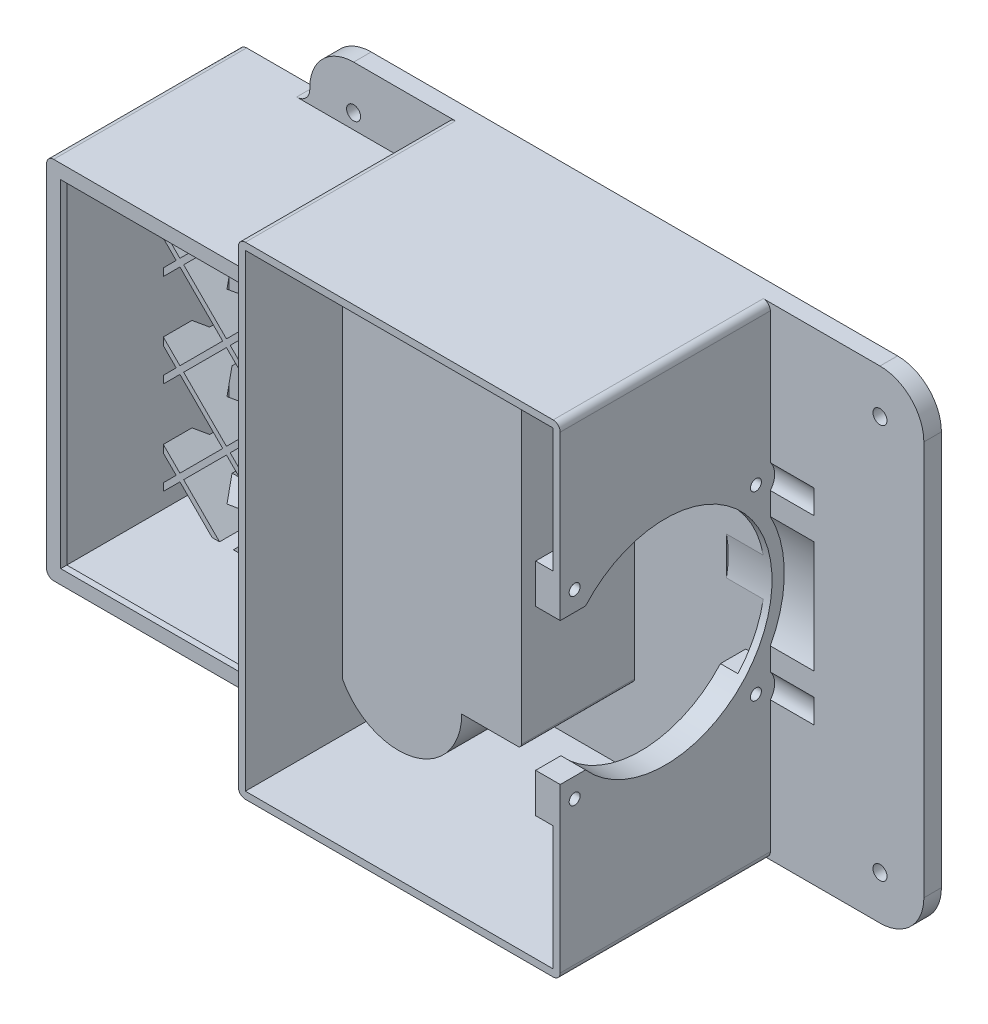
SolidWorks part; units mm, degrees
ref_plane "Front Plane" through (0, 0, 0) normal (0, 0, 1) x (1, 0, 0)
ref_plane "Top Plane" through (0, 0, 0) normal (0, 1, 0) x (1, 0, 0)
ref_plane "Right Plane" through (0, 0, 0) normal (1, 0, 0) x (0, 0, -1)
sketch "Sketch11" plane through (0, 0, 0) normal (0, 0, 1) x (1, 0, 0)
  line L0 (-18.2, 15.22) -> (0, 15.22)
  line L1 (0, 15.22) -> (0, 13.61)
  line L2 (-18.2, 13.61) -> (0, 13.61)
  line L3 (-18.2, 0) -> (0, 0)
  line L4 (0, 0) -> (0, 1.61)
  line L5 (-18.2, 1.61) -> (0, 1.61)
  line L6 (-25.81, 7.61) -> (0, 7.61)
  arc A0 (-18.2, 13.61) -> (-18.2, 1.61) centre (-18.2, 7.61) ccw
  arc A1 (-18.2, 15.22) -> (-18.2, 0) centre (-18.2, 7.61) ccw
sketch "Sketch1" plane through (0, 0, 0) normal (0, 0, 1) x (1, 0, 0)
  line L1 (160, 10) -> (160, 100)
  line L2 (150, 0) -> (30, 0)
  line L3 (20, 10) -> (20, 10.39)
  line L4 (150, 110) -> (30, 110)
  line L10 (1.61, 96.61) -> (17, 96.61)
  line L11 (17, 13.39) -> (1.61, 13.39)
  line L12 (0, 15) -> (0, 95)
  line L17 (20, 99.61) -> (20, 100)
  circle A8 centre (30, 10) radius 1.6
  circle A9 centre (30, 100) radius 1.6
  circle A10 centre (150, 10) radius 1.6
  circle A11 centre (150, 100) radius 1.6
  arc A12 (1.61, 96.61) -> (0, 95) centre (1.61, 95) ccw
  arc A14 (0, 15) -> (1.61, 13.39) centre (1.61, 15) ccw
  arc A16 (17, 96.61) -> (20, 99.61) centre (17, 99.61) ccw
  arc A17 (17, 13.39) -> (20, 10.39) centre (17, 10.39) cw
  arc A18 (20, 10) -> (30, 0) centre (30, 10) ccw
  arc A19 (30, 110) -> (20, 100) centre (30, 100) ccw
  arc A20 (160, 100) -> (150, 110) centre (150, 100) ccw
  arc A21 (150, 0) -> (160, 10) centre (150, 10) ccw
extrude "Boss-Extrude1" add sketch "Sketch1" along normal blind 4
sketch "Sketch3" plane through (0, 0, 4) normal (0, 0, 1) x (1, 0, 0)
  line L0 (1.61, 83.8886) -> (1.61, 82.1774)
  line L2 (19.2854, 95) -> (26.61, 87.6754)
  line L3 (26.61, 87.6754) -> (33.9346, 95)
  line L5 (33.9346, 95) -> (35.6458, 95)
  line L6 (17.5742, 95) -> (19.2854, 95)
  line L7 (6.2524, 86.8198) -> (14.4326, 95)
  line L8 (6.2524, 86.8198) -> (16.0034, 77.0688)
  line L9 (16.0034, 77.0688) -> (25.7544, 86.8198)
  line L10 (17.5742, 95) -> (25.7544, 86.8198)
  line L11 (38.7874, 95) -> (40.4986, 95)
  line L12 (51.61, 83.8886) -> (51.61, 82.1774)
  line L13 (1.61, 82.1774) -> (5.3968, 85.9642)
  line L14 (1.61, 70.249) -> (5.3968, 66.4622)
  line L15 (5.3968, 66.4622) -> (15.1478, 76.2132)
  line L16 (5.3968, 85.9642) -> (15.1478, 76.2132)
  line L17 (51.61, 70.249) -> (51.61, 68.5378)
  line L18 (1.61, 70.249) -> (1.61, 68.5378)
  line L21 (1.61, 62.6754) -> (4.5412, 65.6066)
  line L22 (1.61, 68.5378) -> (4.5412, 65.6066)
  line L23 (1.61, 62.6754) -> (1.61, 60.9642)
  line L24 (1.61, 49.0358) -> (1.61, 47.3246)
  line L29 (1.61, 41.4622) -> (1.61, 39.751)
  line L30 (1.61, 27.8226) -> (1.61, 26.1114)
  line L35 (1.61, 20.249) -> (1.61, 18.5378)
  line L36 (33.9346, 15) -> (35.6458, 15)
  line L37 (27.4656, 86.8198) -> (35.6458, 95)
  line L38 (27.4656, 86.8198) -> (37.2166, 77.0688)
  line L39 (37.2166, 77.0688) -> (46.9676, 86.8198)
  line L40 (38.7874, 95) -> (46.9676, 86.8198)
  line L41 (17.5742, 15) -> (19.2854, 15)
  line L42 (38.7874, 15) -> (40.4986, 15)
  line L43 (16.859, 76.2132) -> (26.61, 85.9642)
  line L44 (16.859, 76.2132) -> (26.61, 66.4622)
  line L45 (26.61, 66.4622) -> (36.361, 76.2132)
  line L46 (26.61, 85.9642) -> (36.361, 76.2132)
  line L47 (51.61, 20.249) -> (51.61, 18.5378)
  line L48 (51.61, 27.8226) -> (51.61, 26.1114)
  line L49 (6.2524, 65.6066) -> (16.0034, 75.3576)
  line L50 (6.2524, 65.6066) -> (16.0034, 55.8556)
  line L51 (16.0034, 55.8556) -> (25.7544, 65.6066)
  line L52 (16.0034, 75.3576) -> (25.7544, 65.6066)
  line L53 (51.61, 41.4622) -> (51.61, 39.751)
  line L54 (51.61, 49.0358) -> (51.61, 47.3246)
  line L55 (1.61, 60.9642) -> (5.3968, 64.751)
  line L56 (1.61, 49.0358) -> (5.3968, 45.249)
  line L57 (5.3968, 45.249) -> (15.1478, 55)
  line L58 (5.3968, 64.751) -> (15.1478, 55)
  line L59 (51.61, 62.6754) -> (51.61, 60.9642)
  line L63 (1.61, 41.4622) -> (4.5412, 44.3934)
  line L64 (1.61, 47.3246) -> (4.5412, 44.3934)
  line L73 (38.0722, 76.2132) -> (47.8232, 85.9642)
  line L74 (38.0722, 76.2132) -> (47.8232, 66.4622)
  line L75 (47.8232, 66.4622) -> (51.61, 70.249)
  line L76 (47.8232, 85.9642) -> (51.61, 82.1774)
  line L79 (27.4656, 65.6066) -> (37.2166, 75.3576)
  line L80 (27.4656, 65.6066) -> (37.2166, 55.8556)
  line L81 (37.2166, 55.8556) -> (46.9676, 65.6066)
  line L82 (37.2166, 75.3576) -> (46.9676, 65.6066)
  line L85 (16.859, 55) -> (26.61, 64.751)
  line L86 (16.859, 55) -> (26.61, 45.249)
  line L87 (26.61, 45.249) -> (36.361, 55)
  line L88 (26.61, 64.751) -> (36.361, 55)
  line L91 (6.2524, 44.3934) -> (16.0034, 54.1444)
  line L92 (6.2524, 44.3934) -> (16.0034, 34.6424)
  line L93 (16.0034, 34.6424) -> (25.7544, 44.3934)
  line L94 (16.0034, 54.1444) -> (25.7544, 44.3934)
  line L97 (1.61, 39.751) -> (5.3968, 43.5378)
  line L98 (1.61, 27.8226) -> (5.3968, 24.0358)
  line L99 (5.3968, 24.0358) -> (15.1478, 33.7868)
  line L100 (5.3968, 43.5378) -> (15.1478, 33.7868)
  line L105 (1.61, 20.249) -> (4.5412, 23.1802)
  line L106 (1.61, 26.1114) -> (4.5412, 23.1802)
  line L109 (48.6788, 65.6066) -> (51.61, 68.5378)
  line L110 (48.6788, 65.6066) -> (51.61, 62.6754)
  line L115 (38.0722, 55) -> (47.8232, 64.751)
  line L116 (38.0722, 55) -> (47.8232, 45.249)
  line L117 (47.8232, 45.249) -> (51.61, 49.0358)
  line L118 (47.8232, 64.751) -> (51.61, 60.9642)
  line L121 (27.4656, 44.3934) -> (37.2166, 54.1444)
  line L122 (27.4656, 44.3934) -> (37.2166, 34.6424)
  line L123 (37.2166, 34.6424) -> (46.9676, 44.3934)
  line L124 (37.2166, 54.1444) -> (46.9676, 44.3934)
  line L127 (16.859, 33.7868) -> (26.61, 43.5378)
  line L128 (16.859, 33.7868) -> (26.61, 24.0358)
  line L129 (26.61, 24.0358) -> (36.361, 33.7868)
  line L130 (26.61, 43.5378) -> (36.361, 33.7868)
  line L133 (6.2524, 23.1802) -> (16.0034, 32.9312)
  line L134 (6.2524, 23.1802) -> (14.4326, 15)
  line L135 (17.5742, 15) -> (25.7544, 23.1802)
  line L136 (16.0034, 32.9312) -> (25.7544, 23.1802)
  line L139 (1.61, 18.5378) -> (5.3968, 22.3246)
  line L142 (5.3968, 22.3246) -> (12.7214, 15)
  line L151 (48.6788, 44.3934) -> (51.61, 47.3246)
  line L152 (48.6788, 44.3934) -> (51.61, 41.4622)
  line L157 (38.0722, 33.7868) -> (47.8232, 43.5378)
  line L158 (38.0722, 33.7868) -> (47.8232, 24.0358)
  line L159 (47.8232, 24.0358) -> (51.61, 27.8226)
  line L160 (47.8232, 43.5378) -> (51.61, 39.751)
  line L163 (27.4656, 23.1802) -> (37.2166, 32.9312)
  line L164 (27.4656, 23.1802) -> (35.6458, 15)
  line L165 (38.7874, 15) -> (46.9676, 23.1802)
  line L166 (37.2166, 32.9312) -> (46.9676, 23.1802)
  line L169 (19.2854, 15) -> (26.61, 22.3246)
  line L172 (26.61, 22.3246) -> (33.9346, 15)
  line L193 (48.6788, 23.1802) -> (51.61, 26.1114)
  line L194 (48.6788, 23.1802) -> (51.61, 20.249)
  line L199 (40.4986, 15) -> (47.8232, 22.3246)
  line L202 (47.8232, 22.3246) -> (51.61, 18.5378)
  line L222 (1.61, 91.4622) -> (5.3968, 87.6754)
  line L223 (5.3968, 87.6754) -> (12.7214, 95)
  line L228 (1.61, 83.8886) -> (4.5412, 86.8198)
  line L229 (1.61, 89.751) -> (4.5412, 86.8198)
  line L253 (40.4986, 95) -> (47.8232, 87.6754)
  line L254 (47.8232, 87.6754) -> (51.61, 91.4622)
  line L257 (48.6788, 86.8198) -> (51.61, 89.751)
  line L258 (48.6788, 86.8198) -> (51.61, 83.8886)
  line L281 (12.7214, 95) -> (14.4326, 95)
  line L284 (1.61, 91.4622) -> (1.61, 89.751)
  line L285 (12.7214, 15) -> (14.4326, 15)
  line L286 (51.61, 91.4622) -> (51.61, 89.751)
extrude "Boss-Extrude3" add sketch "Sketch3" along normal blind 15
sketch "Sketch4" plane through (12.7493, -12.7493, 0) normal (0.7071, -0.7071, 0) x (0, 0, -1)
  line L22 (-4, 23.812) -> (-4, 31.602)
  line L25 (-14, 27.707) -> (-10.105, 23.812)
  line L26 (-10.105, 23.812) -> (-4, 23.812)
  line L27 (-14, 27.707) -> (-10.105, 31.602)
  line L28 (-10.105, 31.602) -> (-4, 31.602)
  line L29 (-4, 8.812) -> (-4, 16.602)
  line L36 (-14, 12.707) -> (-10.105, 8.812)
  line L42 (-10.105, 8.812) -> (-4, 8.812)
  line L43 (-14, 12.707) -> (-10.105, 16.602)
  line L44 (-10.105, 16.602) -> (-4, 16.602)
  line L46 (-4, 38.812) -> (-4, 46.602)
  line L48 (-14, 42.707) -> (-10.105, 38.812)
  line L49 (-10.105, 38.812) -> (-4, 38.812)
  line L50 (-14, 42.707) -> (-10.105, 46.602)
  line L51 (-10.105, 46.602) -> (-4, 46.602)
  line L53 (-4, 53.812) -> (-4, 61.602)
  line L55 (-14, 57.707) -> (-10.105, 53.812)
  line L56 (-10.105, 53.812) -> (-4, 53.812)
  line L57 (-14, 57.707) -> (-10.105, 61.602)
  line L58 (-10.105, 61.602) -> (-4, 61.602)
  line L60 (-4, 68.812) -> (-4, 76.602)
  line L62 (-14, 72.707) -> (-10.105, 68.812)
  line L63 (-10.105, 68.812) -> (-4, 68.812)
  line L64 (-14, 72.707) -> (-10.105, 76.602)
  line L65 (-10.105, 76.602) -> (-4, 76.602)
  line L67 (-4, 83.812) -> (-4, 91.602)
  line L69 (-14, 87.707) -> (-10.105, 83.812)
  line L70 (-10.105, 83.812) -> (-4, 83.812)
  line L71 (-14, 87.707) -> (-10.105, 91.602)
  line L72 (-10.105, 91.602) -> (-4, 91.602)
  line L74 (-4, 98.812) -> (-4, 106.602)
  line L76 (-14, 102.707) -> (-10.105, 98.812)
  line L77 (-10.105, 98.812) -> (-4, 98.812)
  line L78 (-14, 102.707) -> (-10.105, 106.602)
  line L79 (-10.105, 106.602) -> (-4, 106.602)
extrude "Cut-Extrude1" cut sketch "Sketch4" against normal up to surface (76.21 mm away) up to face at (9.0591, 91.3377, 11.5)
sketch "Sketch5" plane through (13.8607, 13.8607, 0) normal (-0.7071, -0.7071, 0) x (0, 0, 1)
  line L15 (4, 16.1798) -> (4, 23.9698)
  line L35 (10.105, 68.9698) -> (4, 68.9698)
  line L36 (14, 65.0748) -> (10.105, 68.9698)
  line L37 (10.105, 61.1798) -> (4, 61.1798)
  line L38 (14, 65.0748) -> (10.105, 61.1798)
  line L39 (4, 61.1798) -> (4, 68.9698)
  line L40 (10.105, 53.9698) -> (4, 53.9698)
  line L41 (14, 50.0748) -> (10.105, 53.9698)
  line L42 (10.105, 46.1798) -> (4, 46.1798)
  line L43 (14, 50.0748) -> (10.105, 46.1798)
  line L44 (4, 46.1798) -> (4, 53.9698)
  line L45 (10.105, 38.9698) -> (4, 38.9698)
  line L46 (14, 35.0748) -> (10.105, 38.9698)
  line L47 (10.105, 31.1798) -> (4, 31.1798)
  line L48 (14, 35.0748) -> (10.105, 31.1798)
  line L49 (4, 31.1798) -> (4, 38.9698)
  line L50 (10.105, 23.9698) -> (4, 23.9698)
  line L51 (14, 20.0748) -> (10.105, 23.9698)
  line L52 (10.105, 16.1798) -> (4, 16.1798)
  line L53 (14, 20.0748) -> (10.105, 16.1798)
  line L54 (10.105, 8.9698) -> (4, 8.9698)
  line L55 (14, 5.0748) -> (10.105, 8.9698)
  line L56 (10.105, 1.1798) -> (4, 1.1798)
  line L57 (14, 5.0748) -> (10.105, 1.1798)
  line L58 (4, 1.1798) -> (4, 8.9698)
  line L59 (10.105, -21.0302) -> (4, -21.0302)
  line L60 (14, -24.9252) -> (10.105, -21.0302)
  line L61 (10.105, -28.8202) -> (4, -28.8202)
  line L62 (14, -24.9252) -> (10.105, -28.8202)
  line L63 (4, -28.8202) -> (4, -21.0302)
  line L64 (10.105, -6.0302) -> (4, -6.0302)
  line L65 (14, -9.9252) -> (10.105, -6.0302)
  line L66 (10.105, -13.8202) -> (4, -13.8202)
  line L67 (14, -9.9252) -> (10.105, -13.8202)
  line L68 (4, -13.8202) -> (4, -6.0302)
extrude "Cut-Extrude2" cut sketch "Sketch5" against normal up to surface (76.21 mm away) up to face at (44.1609, 91.3377, 11.5)
sketch "Sketch2" plane through (0, 0, 4) normal (0, 0, 1) x (1, 0, 0)
  line L1 (1.61, 95) -> (51.61, 95)
  line L2 (1.61, 95) -> (1.61, 15)
  line L3 (1.61, 15) -> (51.61, 15)
  line L4 (51.61, 95) -> (51.61, 15)
  line L11 (0, 15) -> (0, 95)
  line L13 (1.61, 13.39) -> (53.22, 13.39)
  line L15 (1.61, 96.61) -> (53.22, 96.61)
  line L16 (53.22, 13.39) -> (53.22, 96.61)
  arc A4 (1.61, 96.61) -> (0, 95) centre (1.61, 95) ccw
  arc A7 (0, 15) -> (1.61, 13.39) centre (1.61, 15) ccw
extrude "Boss-Extrude2" add sketch "Sketch2" along normal blind 40
sketch "Sketch6" plane through (0, 15, 0) normal (0, 1, 0) x (1, 0, 0)
  line L0 (51.61, -44) -> (51.61, -41)
  line L2 (51.61, -44) -> (50.01, -44)
  line L4 (51.61, -41) -> (50.01, -42.6)
  line L5 (50.01, -42.6) -> (50.01, -44)
  line L6 (1.61, -44) -> (1.61, -41)
  line L10 (3.21, -42.6) -> (3.21, -44)
  line L11 (1.61, -41) -> (3.21, -42.6)
  line L12 (1.61, -44) -> (3.21, -44)
extrude "Boss-Extrude4" add sketch "Sketch6" along normal up to surface (80 mm away) up to face at (26.61, 95, 12.9488)
sketch "Sketch7" plane through (51.61, 0, 0) normal (-1, 0, 0) x (0, 0, 1)
  line L0 (44, 95) -> (41, 95)
  line L1 (44, 95) -> (44, 93.4)
  line L2 (41, 95) -> (42.6, 93.4)
  line L3 (42.6, 93.4) -> (44, 93.4)
  line L4 (44, 15) -> (41, 15)
  line L8 (42.6, 16.6) -> (44, 16.6)
  line L9 (41, 15) -> (42.6, 16.6)
  line L10 (44, 15) -> (44, 16.6)
extrude "Boss-Extrude5" add sketch "Sketch7" along normal up to surface (50 mm away) up to face at (1.61, 40.6066, 15.4277)
sketch "Sketch22" plane through (0, 0, 4) normal (0, 0, 1) x (1, 0, 0)
  line L0 (53.22, 1.61) -> (53.22, 108.39)
  line L2 (53.22, 108.39) -> (123.39, 108.39)
  line L3 (51.61, 1.61) -> (51.61, 108.39)
  line L5 (123.39, 1.61) -> (123.39, 108.39)
  line L6 (53.22, 0) -> (123.39, 0)
  line L7 (125, 1.61) -> (125, 108.39)
  line L8 (53.22, 1.61) -> (123.39, 1.61)
  line L9 (53.22, 110) -> (123.39, 110)
  arc A0 (53.22, 110) -> (51.61, 108.39) centre (53.22, 108.39) ccw
  arc A1 (51.61, 1.61) -> (53.22, 0) centre (53.22, 1.61) ccw
  arc A4 (125, 1.61) -> (123.39, 0) centre (123.39, 1.61) cw
  arc A5 (123.39, 110) -> (125, 108.39) centre (123.39, 108.39) cw
extrude "Boss-Extrude8" add sketch "Sketch22" along normal blind 47.9
sketch "Sketch23" plane through (125, 0, 0) normal (1, 0, 0) x (0, 0, -1)
  line L8 (-4, 31.5988) -> (-4, 37.0779)
  line L9 (-4, 42.2338) -> (-4, 67.7662)
  line L10 (-4, 72.9221) -> (-4, 78.4012)
  arc A26 (-4, 31.5988) -> (-4, 37.0779) centre (-7.2883, 34.3383) ccw
  arc A28 (-4, 72.9221) -> (-4, 78.4012) centre (-7.2883, 75.6617) ccw
  arc A30 (-4, 42.2338) -> (-4, 67.7662) centre (-27.95, 55) ccw
extrude "Cut-Extrude6" cut sketch "Sketch23" along normal blind 10
sketch "Sketch24" plane through (125, 0, 0) normal (1, 0, 0) x (0, 0, -1)
  line L2 (-51.9, 38.8183) -> (-46.1321, 38.8183)
  line L14 (-51.9, 71.1817) -> (-46.1321, 71.1817)
  line L36 (-51.9, 38.8183) -> (-51.9, 71.1817)
  circle A9 centre (-48.6117, 34.3383) radius 1.25
  circle A11 centre (-7.2883, 34.3383) radius 1.25
  circle A12 centre (-7.2883, 75.6617) radius 1.25
  circle A30 centre (-48.6117, 75.6617) radius 1.25
  arc A33 (-46.1321, 38.8183) -> (-46.1321, 71.1817) centre (-27.95, 55) ccw
extrude "Cut-Extrude7" cut sketch "Sketch24" against normal blind 10
sketch "Sketch25" plane through (123.39, 0, 0) normal (-1, 0, 0) x (0, 0, 1)
  line L23 (51.9, 71.1817) -> (51.9, 80.1417)
  line L28 (51.9, 29.8583) -> (41.0287, 29.8583)
  line L29 (51.9, 29.8583) -> (51.9, 38.8183)
  line L30 (51.9, 80.1417) -> (41.0287, 80.1417)
  line L31 (4, 29.8583) -> (4, 38.8183)
  line L32 (51.9, 38.8183) -> (46.1321, 38.8183)
  line L34 (51.9, 71.1817) -> (46.1321, 71.1817)
  line L37 (14.8713, 80.1417) -> (4, 80.1417)
  line L38 (9.7679, 71.1817) -> (4, 71.1817)
  line L39 (9.7679, 38.8183) -> (4, 38.8183)
  line L40 (4, 71.1817) -> (4, 80.1417)
  line L41 (14.8713, 29.8583) -> (4, 29.8583)
  circle A13 centre (48.6117, 34.3383) radius 1.25
  circle A15 centre (48.6117, 75.6617) radius 1.25
  circle A16 centre (7.2883, 75.6617) radius 1.25
  circle A17 centre (7.2883, 34.3383) radius 1.25
  arc A20 (46.1321, 71.1817) -> (9.7679, 71.1817) centre (27.95, 55) ccw
  arc A21 (41.0287, 80.1417) -> (14.8713, 80.1417) centre (27.95, 55) ccw
  arc A22 (9.7679, 38.8183) -> (46.1321, 38.8183) centre (27.95, 55) ccw
  arc A24 (14.8713, 29.8583) -> (41.0287, 29.8583) centre (27.95, 55) ccw
extrude "Boss-Extrude9" add sketch "Sketch25" along normal blind 4
sketch "Sketch15" plane through (53.22, 0, 0) normal (1, 0, 0) x (0, 0, -1)
  line L0 (-4, 25.1802) -> (-4, 42.3934)
  line L1 (-4, 46.3934) -> (-4, 63.6066)
  line L2 (-4, 67.6066) -> (-4, 84.8198)
  line L4 (-16, 33.7868) -> (-7.3934, 42.3934)
  line L5 (-7.3934, 42.3934) -> (-4, 42.3934)
  line L6 (-16, 55) -> (-7.3934, 46.3934)
  line L7 (-7.3934, 46.3934) -> (-4, 46.3934)
  line L9 (-16, 55) -> (-7.3934, 63.6066)
  line L12 (-7.3934, 63.6066) -> (-4, 63.6066)
  line L13 (-16, 76.2132) -> (-7.3934, 67.6066)
  line L14 (-7.3934, 67.6066) -> (-4, 67.6066)
  line L15 (-16, 76.2132) -> (-7.3934, 84.8198)
  line L20 (-7.3934, 84.8198) -> (-4, 84.8198)
  line L21 (-16, 33.7868) -> (-7.3934, 25.1802)
  line L30 (-7.3934, 25.1802) -> (-4, 25.1802)
extrude "Cut-Extrude5" cut sketch "Sketch15" against normal up to surface (1.61 mm away) up to face at (51.61, 69.3934, 15.4277)
sketch "Sketch9" plane through (0, 0, 4) normal (0, 0, 1) x (1, 0, 0)
  line L15 (51.61, 94.9747) -> (51.61, 96.61)
  line L16 (51.61, 96.61) -> (52.415, 96.61)
  line L17 (65.22, 88.815) -> (65.22, 90.585)
  line L19 (51.61, 19.415) -> (53.22, 19.415)
  line L29 (78.83, 19.415) -> (78.83, 90.585)
  line L31 (66.83, 90.585) -> (66.83, 19.415)
  line L32 (65.22, 19.415) -> (65.22, 82.195)
  line L36 (80.44, 90.585) -> (80.44, 19.415)
  line L37 (92.44, 90.585) -> (92.44, 20.22)
  line L38 (94.05, 90.585) -> (94.05, 20.22)
  arc A36 (65.22, 88.815) -> (52.415, 96.61) centre (52.415, 82.195) ccw
  arc A37 (65.22, 82.195) -> (51.61, 94.9747) centre (52.415, 82.195) ccw
  arc A38 (65.22, 19.415) -> (66.83, 19.415) centre (66.025, 19.415) ccw
  arc A42 (53.22, 19.415) -> (78.83, 19.415) centre (66.025, 19.415) ccw
  arc A47 (51.61, 19.415) -> (80.44, 19.415) centre (66.025, 19.415) ccw
  arc A48 (80.44, 90.585) -> (78.83, 90.585) centre (79.635, 90.585) ccw
  arc A49 (92.44, 90.585) -> (66.83, 90.585) centre (79.635, 90.585) ccw
  arc A50 (94.05, 90.585) -> (65.22, 90.585) centre (79.635, 90.585) ccw
  arc A51 (92.44, 20.22) -> (94.05, 20.22) centre (93.245, 20.22) ccw
extrude "Boss-Extrude6" add sketch "Sketch9" along normal blind 24.2
sketch "Sketch12" plane through (0, 0, 28.2) normal (0, 0, 1) x (1, 0, 0)
  line L2 (51.61, 96.61) -> (52.415, 96.61)
  line L4 (65.22, 88.815) -> (65.22, 90.585)
  line L11 (94.05, 90.585) -> (94.05, 20.22)
  line L12 (93.245, 19.415) -> (80.44, 19.415)
  line L14 (53.22, 15) -> (53.22, 95)
  arc A7 (65.22, 88.815) -> (52.415, 96.61) centre (52.415, 82.195) ccw
  arc A18 (94.05, 90.585) -> (65.22, 90.585) centre (79.635, 90.585) ccw
  arc A19 (93.245, 19.415) -> (94.05, 20.22) centre (93.245, 20.22) ccw
  arc A20 (53.22, 95) -> (51.61, 96.61) centre (51.61, 95) ccw
  arc A22 (52.7302, 13.8436) -> (80.44, 19.415) centre (66.025, 19.415) ccw
  arc A23 (52.7302, 13.8436) -> (53.22, 15) centre (51.61, 15) ccw
extrude "Boss-Extrude7" add sketch "Sketch12" along normal blind 1.6
fillet "Fillet1" radius 6 12 edges at (61.7498, 90.9603, 28.2) (65.22, 50.805, 28.2) (66.025, 18.61, 28.2) (66.83, 55, 28.2) (79.635, 103.39, 28.2) (92.6758, 19.6508, 28.2) (66.025, 6.61, 28.2) (78.83, 55, 28.2) (79.635, 91.39, 28.2) (92.44, 55.4025, 28.2) (80.44, 55, 28.2) (53.22, 57.1948, 28.2)
